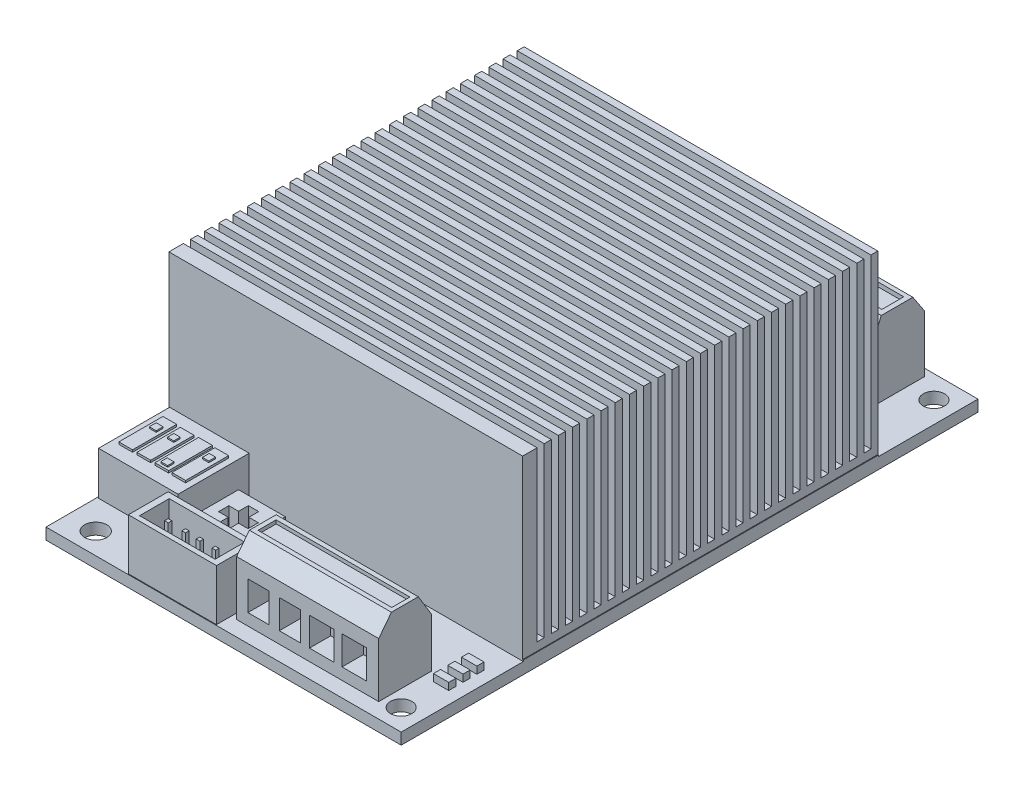
SolidWorks part; units mm, degrees
ref_plane "Front Plane" through (0, 0, 0) normal (0, 0, 1) x (1, 0, 0)
ref_plane "Top Plane" through (0, 0, 0) normal (0, 1, 0) x (1, 0, 0)
ref_plane "Right Plane" through (0, 0, 0) normal (1, 0, 0) x (0, 0, -1)
ref_plane "Plane1" through (0, 0, 0) normal (0, -1, 0) x (1, 0, 0)
sketch "Sketch1" plane through (0, 0, 0) normal (0, -1, 0) x (1, 0, 0)
  line L0 (50, -7.2) -> (0, -7.2)
  line L1 (0, -7.2) -> (0, -81.2)
  line L2 (0, -81.2) -> (50, -81.2)
  line L3 (50, -81.2) -> (50, -7.2)
extrude "Boss-Extrude1" add sketch "Sketch1" against normal blind 26.6
sketch "Sketch2" plane through (50, 0, 0) normal (1, 0, 0) x (0, 0, -1)
  line L0 (67.2, 26.6) -> (67.2, 1.6)
  line L1 (81.2, 1.6) -> (81.2, 26.6)
  line L2 (81.2, 26.6) -> (67.2, 26.6)
  spline S0 degree 1 poles (67.2, 1.6) (80, 1.6) (81.2, 1.6) knots 0 0 1 1.09375 1.09375
extrude "Cut-Extrude1" cut sketch "Sketch2" against normal through all
sketch "Sketch3" plane through (0, 0, -67.2) normal (0, 0, -1) x (-1, 0, 0)
  line L0 (-0.1, 26.6) -> (-0.1, 1.9034)
  line L1 (-0.1, 1.9034) -> (0, 1.9034)
  line L2 (0, 1.9034) -> (0, 26.6)
  line L3 (0, 26.6) -> (-0.1, 26.6)
extrude "Cut-Extrude2" cut sketch "Sketch3" against normal blind 60
sketch "Sketch4" plane through (0.1, 0, 0) normal (-1, 0, 0) x (0, 0, 1)
  line L0 (-17.2, 26.6) -> (-17.2, 7.7)
  line L1 (-17.2, 7.7) -> (-7.2, 7.7)
  line L2 (-7.2, 7.7) -> (-7.2, 26.6)
  line L3 (-7.2, 26.6) -> (-17.2, 26.6)
extrude "Cut-Extrude3" cut sketch "Sketch4" against normal through all
sketch "Sketch5" plane through (0.1, 0, 0) normal (-1, 0, 0) x (0, 0, 1)
  line L0 (-7.2, 7.7) -> (-17.2, 7.7)
  line L1 (-17.2, 7.7) -> (-17.2, 1.9034)
  line L2 (-17.2, 1.9034) -> (-7.2, 1.9034)
  line L3 (-7.2, 1.9034) -> (-7.2, 7.7)
extrude "Cut-Extrude4" cut sketch "Sketch5" against normal blind 0.1
ref_plane "Plane2" [suppressed] through (0, 0, -17.2) normal (0, 0, 1) x (1, 0, 0)
ref_plane "Plane3" through (0, 0, -17.4899) normal (0, 0, -1) x (-1, 0, 0)
sketch "Sketch7" plane through (0, 0, -17.4899) normal (0, 0, -1) x (-1, 0, 0)
  line L0 (-0.1, 1.9034) -> (-0.1, 8.072)
  line L1 (-0.1, 8.072) -> (-0.2, 8.072)
  line L2 (-0.2, 8.072) -> (-0.2, 1.9034)
  line L3 (-0.2, 1.9034) -> (-0.1, 1.9034)
extrude "Cut-Extrude5" [suppressed] cut sketch "Sketch7" against normal up to surface
sketch "Sketch8" plane through (0, 1.9034, 0) normal (0, 1, 0) x (-1, 0, 0)
  line L0 (0, -17.4899) -> (0, -7.2)
  line L1 (0, -7.2) -> (-0.2, -7.2)
  line L2 (-0.2, -7.2) -> (-0.2, -17.4899)
  line L3 (-0.2, -17.4899) -> (0, -17.4899)
extrude "Cut-Extrude6" cut sketch "Sketch8" against normal blind 0.3034
sketch "Sketch9" plane through (0, 0, -7.2) normal (0, 0, 1) x (1, 0, 0)
  line L0 (50, 0) -> (0, 0)
  line L1 (0, 0) -> (0, 1.6)
  line L2 (0, 1.6) -> (50, 1.6)
  line L3 (50, 1.6) -> (50, 0)
extrude "Boss-Extrude2" add sketch "Sketch9" along normal blind 7.2
ref_plane "Plane4" [suppressed] through (0, 1.6, 0) normal (0, 1, 0) x (1, 0, 0)
ref_plane "Plane5" [suppressed] through (0, 1.1135, 0) normal (0, -1, 0) x (1, 0, 0)
sketch "Sketch11" [suppressed] plane through (0, 1.1135, 0) normal (0, -1, 0) x (1, 0, 0)
  line L0 (0, -17.4899) -> (0.2, -17.4899)
  line L1 (0.2, -17.4899) -> (0.2, -6.7544)
  line L2 (0.2, -6.7544) -> (0, -6.7544)
  line L3 (0, -6.7544) -> (0, -17.4899)
extrude "Cut-Extrude7" [suppressed] cut sketch "Sketch11" against normal up to surface
ref_plane "Plane6" [suppressed] through (0, 1.1135, 0) normal (0, 1, 0) x (1, 0, 0)
ref_plane "Plane7" [suppressed] through (0, 1.0032, 0) normal (0, -1, 0) x (1, 0, 0)
sketch "Sketch13" [suppressed] plane through (0, 1.0032, 0) normal (0, -1, 0) x (1, 0, 0)
  line L0 (0.2, -17.4147) -> (0.2, -6.7544)
  line L1 (0.2, -6.7544) -> (0, -6.7544)
  line L2 (0, -6.7544) -> (0, -17.4147)
  line L3 (0, -17.4147) -> (0.2, -17.4147)
extrude "Cut-Extrude8" [suppressed] cut sketch "Sketch13" against normal up to surface
sketch "Sketch14" plane through (50, 0, 0) normal (1, 0, 0) x (0, 0, -1)
  line L0 (7.2, 7.7) -> (7.2, 1.6)
  line L1 (7.2, 1.6) -> (17.2, 1.6)
  line L2 (17.2, 1.6) -> (17.2, 7.7)
  line L3 (17.2, 7.7) -> (7.2, 7.7)
extrude "Cut-Extrude9" cut sketch "Sketch14" against normal blind 38.6
sketch "Sketch15" plane through (0, 0, -67.2) normal (0, 0, -1) x (-1, 0, 0)
  line L0 (-49.9, 1.7904) -> (-49.9, 26.6)
  line L1 (-49.9, 26.6) -> (-50, 26.6)
  line L2 (-50, 26.6) -> (-50, 1.7904)
  line L3 (-50, 1.7904) -> (-49.9, 1.7904)
extrude "Cut-Extrude10" cut sketch "Sketch15" against normal blind 50
sketch "Sketch16" plane through (0.1, 0, 0) normal (-1, 0, 0) x (0, 0, 1)
  line L0 (-65.2338, 26.6) -> (-66.2338, 26.6)
  line L1 (-66.2338, 26.6) -> (-66.2338, 2.9373)
  line L2 (-66.2338, 2.9373) -> (-65.2338, 2.9373)
  line L3 (-65.2338, 2.9373) -> (-65.2338, 26.6)
extrude "Cut-Extrude11" cut sketch "Sketch16" against normal through all
sketch "Sketch17" plane through (0.1, 0, 0) normal (-1, 0, 0) x (0, 0, 1)
  line L0 (-63.2338, 26.6) -> (-64.2338, 26.6)
  line L1 (-64.2338, 26.6) -> (-64.2338, 2.9373)
  line L2 (-64.2338, 2.9373) -> (-63.2338, 2.9373)
  line L3 (-63.2338, 2.9373) -> (-63.2338, 26.6)
extrude "Cut-Extrude12" cut sketch "Sketch17" against normal through all
sketch "Sketch18" plane through (0.1, 0, 0) normal (-1, 0, 0) x (0, 0, 1)
  line L0 (-61.2338, 26.6) -> (-62.2338, 26.6)
  line L1 (-62.2338, 26.6) -> (-62.2338, 2.9373)
  line L2 (-62.2338, 2.9373) -> (-61.2338, 2.9373)
  line L3 (-61.2338, 2.9373) -> (-61.2338, 26.6)
extrude "Cut-Extrude13" cut sketch "Sketch18" against normal through all
sketch "Sketch19" plane through (0.1, 0, 0) normal (-1, 0, 0) x (0, 0, 1)
  line L0 (-59.2338, 26.6) -> (-60.2338, 26.6)
  line L1 (-60.2338, 26.6) -> (-60.2338, 2.9373)
  line L2 (-60.2338, 2.9373) -> (-59.2338, 2.9373)
  line L3 (-59.2338, 2.9373) -> (-59.2338, 26.6)
extrude "Cut-Extrude14" cut sketch "Sketch19" against normal through all
sketch "Sketch20" plane through (0.1, 0, 0) normal (-1, 0, 0) x (0, 0, 1)
  line L0 (-57.2338, 26.6) -> (-58.2338, 26.6)
  line L1 (-58.2338, 26.6) -> (-58.2338, 2.9373)
  line L2 (-58.2338, 2.9373) -> (-57.2338, 2.9373)
  line L3 (-57.2338, 2.9373) -> (-57.2338, 26.6)
extrude "Cut-Extrude15" cut sketch "Sketch20" against normal through all
sketch "Sketch21" plane through (0.1, 0, 0) normal (-1, 0, 0) x (0, 0, 1)
  line L0 (-55.2338, 26.6) -> (-56.2338, 26.6)
  line L1 (-56.2338, 26.6) -> (-56.2338, 2.9373)
  line L2 (-56.2338, 2.9373) -> (-55.2338, 2.9373)
  line L3 (-55.2338, 2.9373) -> (-55.2338, 26.6)
extrude "Cut-Extrude16" cut sketch "Sketch21" against normal through all
sketch "Sketch22" plane through (0.1, 0, 0) normal (-1, 0, 0) x (0, 0, 1)
  line L0 (-53.2338, 26.6) -> (-54.2338, 26.6)
  line L1 (-54.2338, 26.6) -> (-54.2338, 2.9373)
  line L2 (-54.2338, 2.9373) -> (-53.2338, 2.9373)
  line L3 (-53.2338, 2.9373) -> (-53.2338, 26.6)
extrude "Cut-Extrude17" cut sketch "Sketch22" against normal through all
sketch "Sketch23" plane through (0.1, 0, 0) normal (-1, 0, 0) x (0, 0, 1)
  line L0 (-51.2338, 26.6) -> (-52.2338, 26.6)
  line L1 (-52.2338, 26.6) -> (-52.2338, 2.9373)
  line L2 (-52.2338, 2.9373) -> (-51.2338, 2.9373)
  line L3 (-51.2338, 2.9373) -> (-51.2338, 26.6)
extrude "Cut-Extrude18" cut sketch "Sketch23" against normal through all
sketch "Sketch24" plane through (0.1, 0, 0) normal (-1, 0, 0) x (0, 0, 1)
  line L0 (-49.2338, 26.6) -> (-50.2338, 26.6)
  line L1 (-50.2338, 26.6) -> (-50.2338, 2.9373)
  line L2 (-50.2338, 2.9373) -> (-49.2338, 2.9373)
  line L3 (-49.2338, 2.9373) -> (-49.2338, 26.6)
extrude "Cut-Extrude19" cut sketch "Sketch24" against normal through all
sketch "Sketch25" plane through (0.1, 0, 0) normal (-1, 0, 0) x (0, 0, 1)
  line L0 (-47.2338, 26.6) -> (-48.2338, 26.6)
  line L1 (-48.2338, 26.6) -> (-48.2338, 2.9373)
  line L2 (-48.2338, 2.9373) -> (-47.2338, 2.9373)
  line L3 (-47.2338, 2.9373) -> (-47.2338, 26.6)
extrude "Cut-Extrude20" cut sketch "Sketch25" against normal through all
sketch "Sketch26" plane through (0.1, 0, 0) normal (-1, 0, 0) x (0, 0, 1)
  line L0 (-45.2338, 26.6) -> (-46.2338, 26.6)
  line L1 (-46.2338, 26.6) -> (-46.2338, 2.9373)
  line L2 (-46.2338, 2.9373) -> (-45.2338, 2.9373)
  line L3 (-45.2338, 2.9373) -> (-45.2338, 26.6)
extrude "Cut-Extrude21" cut sketch "Sketch26" against normal through all
sketch "Sketch27" plane through (0.1, 0, 0) normal (-1, 0, 0) x (0, 0, 1)
  line L0 (-43.2338, 26.6) -> (-44.2338, 26.6)
  line L1 (-44.2338, 26.6) -> (-44.2338, 2.9373)
  line L2 (-44.2338, 2.9373) -> (-43.2338, 2.9373)
  line L3 (-43.2338, 2.9373) -> (-43.2338, 26.6)
extrude "Cut-Extrude22" cut sketch "Sketch27" against normal through all
sketch "Sketch28" plane through (0.1, 0, 0) normal (-1, 0, 0) x (0, 0, 1)
  line L0 (-41.2338, 26.6) -> (-42.2338, 26.6)
  line L1 (-42.2338, 26.6) -> (-42.2338, 2.9373)
  line L2 (-42.2338, 2.9373) -> (-41.2338, 2.9373)
  line L3 (-41.2338, 2.9373) -> (-41.2338, 26.6)
extrude "Cut-Extrude23" cut sketch "Sketch28" against normal through all
sketch "Sketch29" plane through (0.1, 0, 0) normal (-1, 0, 0) x (0, 0, 1)
  line L0 (-39.2338, 26.6) -> (-40.2338, 26.6)
  line L1 (-40.2338, 26.6) -> (-40.2338, 2.9373)
  line L2 (-40.2338, 2.9373) -> (-39.2338, 2.9373)
  line L3 (-39.2338, 2.9373) -> (-39.2338, 26.6)
extrude "Cut-Extrude24" cut sketch "Sketch29" against normal through all
sketch "Sketch30" plane through (0.1, 0, 0) normal (-1, 0, 0) x (0, 0, 1)
  line L0 (-37.2338, 26.6) -> (-38.2338, 26.6)
  line L1 (-38.2338, 26.6) -> (-38.2338, 2.9373)
  line L2 (-38.2338, 2.9373) -> (-37.2338, 2.9373)
  line L3 (-37.2338, 2.9373) -> (-37.2338, 26.6)
extrude "Cut-Extrude25" cut sketch "Sketch30" against normal through all
sketch "Sketch31" plane through (0.1, 0, 0) normal (-1, 0, 0) x (0, 0, 1)
  line L0 (-35.2338, 26.6) -> (-36.2338, 26.6)
  line L1 (-36.2338, 26.6) -> (-36.2338, 2.9373)
  line L2 (-36.2338, 2.9373) -> (-35.2338, 2.9373)
  line L3 (-35.2338, 2.9373) -> (-35.2338, 26.6)
extrude "Cut-Extrude26" cut sketch "Sketch31" against normal through all
sketch "Sketch32" plane through (0.1, 0, 0) normal (-1, 0, 0) x (0, 0, 1)
  line L0 (-33.2338, 26.6) -> (-34.2338, 26.6)
  line L1 (-34.2338, 26.6) -> (-34.2338, 2.9373)
  line L2 (-34.2338, 2.9373) -> (-33.2338, 2.9373)
  line L3 (-33.2338, 2.9373) -> (-33.2338, 26.6)
extrude "Cut-Extrude27" cut sketch "Sketch32" against normal through all
sketch "Sketch33" plane through (0.1, 0, 0) normal (-1, 0, 0) x (0, 0, 1)
  line L0 (-31.2338, 26.6) -> (-32.2338, 26.6)
  line L1 (-32.2338, 26.6) -> (-32.2338, 2.9373)
  line L2 (-32.2338, 2.9373) -> (-31.2338, 2.9373)
  line L3 (-31.2338, 2.9373) -> (-31.2338, 26.6)
extrude "Cut-Extrude28" cut sketch "Sketch33" against normal through all
sketch "Sketch34" plane through (0.1, 0, 0) normal (-1, 0, 0) x (0, 0, 1)
  line L0 (-29.2338, 26.6) -> (-30.2338, 26.6)
  line L1 (-30.2338, 26.6) -> (-30.2338, 2.9373)
  line L2 (-30.2338, 2.9373) -> (-29.2338, 2.9373)
  line L3 (-29.2338, 2.9373) -> (-29.2338, 26.6)
extrude "Cut-Extrude29" cut sketch "Sketch34" against normal through all
sketch "Sketch35" plane through (0.1, 0, 0) normal (-1, 0, 0) x (0, 0, 1)
  line L0 (-27.2338, 26.6) -> (-28.2338, 26.6)
  line L1 (-28.2338, 26.6) -> (-28.2338, 2.9373)
  line L2 (-28.2338, 2.9373) -> (-27.2338, 2.9373)
  line L3 (-27.2338, 2.9373) -> (-27.2338, 26.6)
extrude "Cut-Extrude30" cut sketch "Sketch35" against normal through all
sketch "Sketch36" plane through (0.1, 0, 0) normal (-1, 0, 0) x (0, 0, 1)
  line L0 (-25.2338, 26.6) -> (-26.2338, 26.6)
  line L1 (-26.2338, 26.6) -> (-26.2338, 2.9373)
  line L2 (-26.2338, 2.9373) -> (-25.2338, 2.9373)
  line L3 (-25.2338, 2.9373) -> (-25.2338, 26.6)
extrude "Cut-Extrude31" cut sketch "Sketch36" against normal through all
sketch "Sketch37" plane through (0.1, 0, 0) normal (-1, 0, 0) x (0, 0, 1)
  line L0 (-23.2338, 26.6) -> (-24.2338, 26.6)
  line L1 (-24.2338, 26.6) -> (-24.2338, 2.9373)
  line L2 (-24.2338, 2.9373) -> (-23.2338, 2.9373)
  line L3 (-23.2338, 2.9373) -> (-23.2338, 26.6)
extrude "Cut-Extrude32" cut sketch "Sketch37" against normal through all
sketch "Sketch38" plane through (0.1, 0, 0) normal (-1, 0, 0) x (0, 0, 1)
  line L0 (-21.2338, 26.6) -> (-22.2338, 26.6)
  line L1 (-22.2338, 26.6) -> (-22.2338, 2.9373)
  line L2 (-22.2338, 2.9373) -> (-21.2338, 2.9373)
  line L3 (-21.2338, 2.9373) -> (-21.2338, 26.6)
extrude "Cut-Extrude33" cut sketch "Sketch38" against normal through all
sketch "Sketch39" plane through (0.1, 0, 0) normal (-1, 0, 0) x (0, 0, 1)
  line L0 (-19.2338, 26.6) -> (-20.2338, 26.6)
  line L1 (-20.2338, 26.6) -> (-20.2338, 2.9373)
  line L2 (-20.2338, 2.9373) -> (-19.2338, 2.9373)
  line L3 (-19.2338, 2.9373) -> (-19.2338, 26.6)
extrude "Cut-Extrude34" cut sketch "Sketch39" against normal through all
sketch "Sketch40" plane through (0, 1.6, 0) normal (0, 1, 0) x (-1, 0, 0)
  line L0 (-46.1084, -13.3828) -> (-48.2829, -13.3828)
  line L1 (-48.2829, -13.3828) -> (-48.2829, -12.377)
  line L2 (-48.2829, -12.377) -> (-46.1084, -12.377)
  line L3 (-46.1084, -12.377) -> (-46.1084, -13.3828)
extrude "Boss-Extrude3" add sketch "Sketch40" along normal blind 1
sketch "Sketch41" plane through (0, 1.6, 0) normal (0, 1, 0) x (-1, 0, 0)
  line L0 (-46.1356, -11.4257) -> (-48.2829, -11.4257)
  line L1 (-48.2829, -11.4257) -> (-48.2829, -10.42)
  line L2 (-48.2829, -10.42) -> (-46.1356, -10.42)
  line L3 (-46.1356, -10.42) -> (-46.1356, -11.4257)
extrude "Boss-Extrude4" add sketch "Sketch41" along normal blind 1
sketch "Sketch42" plane through (0, 1.6, 0) normal (0, 1, 0) x (-1, 0, 0)
  line L0 (-46.1356, -9.4142) -> (-48.2829, -9.4142)
  line L1 (-48.2829, -9.4142) -> (-48.2829, -8.4085)
  line L2 (-48.2829, -8.4085) -> (-46.1356, -8.4085)
  line L3 (-46.1356, -8.4085) -> (-46.1356, -9.4142)
extrude "Boss-Extrude5" add sketch "Sketch42" along normal blind 1
sketch "Sketch43" plane through (0, 7.7, 0) normal (0, 1, 0) x (-1, 0, 0)
  line L0 (-5.6278, -15.2126) -> (-5.6278, -9.1046)
  line L1 (-5.6278, -9.1046) -> (-3.6949, -9.1046)
  line L2 (-3.6949, -9.1046) -> (-3.6949, -15.2126)
  line L3 (-3.6949, -15.2126) -> (-5.6278, -15.2126)
extrude "Boss-Extrude6" add sketch "Sketch43" along normal blind 0.3
sketch "Sketch44" plane through (0, 8, 0) normal (0, 1, 0) x (-1, 0, 0)
  line L0 (-5.0896, -13.8034) -> (-5.0896, -12.9014)
  line L1 (-5.0896, -12.9014) -> (-4.1876, -12.9014)
  line L2 (-4.1876, -12.9014) -> (-4.1876, -13.8034)
  line L3 (-4.1876, -13.8034) -> (-5.0896, -13.8034)
extrude "Boss-Extrude7" add sketch "Sketch44" along normal blind 0.2
sketch "Sketch45" plane through (0, 7.7, 0) normal (0, 1, 0) x (-1, 0, 0)
  line L0 (-8.1535, -15.2642) -> (-8.1535, -9.1046)
  line L1 (-8.1535, -9.1046) -> (-6.2206, -9.1046)
  line L2 (-6.2206, -9.1046) -> (-6.2206, -15.2642)
  line L3 (-6.2206, -15.2642) -> (-8.1535, -15.2642)
extrude "Boss-Extrude8" add sketch "Sketch45" along normal blind 0.3
sketch "Sketch46" plane through (0, 8, 0) normal (0, 1, 0) x (-1, 0, 0)
  line L0 (-7.6668, -10.3564) -> (-7.6668, -9.4544)
  line L1 (-7.6668, -9.4544) -> (-6.7004, -9.4544)
  line L2 (-6.7004, -9.4544) -> (-6.7004, -10.3564)
  line L3 (-6.7004, -10.3564) -> (-7.6668, -10.3564)
extrude "Boss-Extrude9" add sketch "Sketch46" along normal blind 0.2
sketch "Sketch47" plane through (0, 7.7, 0) normal (0, 1, 0) x (-1, 0, 0)
  line L0 (-10.5503, -15.1611) -> (-10.5503, -9.1046)
  line L1 (-10.5503, -9.1046) -> (-8.6174, -9.1046)
  line L2 (-8.6174, -9.1046) -> (-8.6174, -15.1611)
  line L3 (-8.6174, -15.1611) -> (-10.5503, -15.1611)
extrude "Boss-Extrude10" add sketch "Sketch47" along normal blind 0.3
sketch "Sketch48" plane through (0, 8, 0) normal (0, 1, 0) x (-1, 0, 0)
  line L0 (-10.0186, -13.8679) -> (-10.0186, -12.9014)
  line L1 (-10.0186, -12.9014) -> (-9.1165, -12.9014)
  line L2 (-9.1165, -12.9014) -> (-9.1165, -13.8679)
  line L3 (-9.1165, -13.8679) -> (-10.0186, -13.8679)
extrude "Boss-Extrude11" add sketch "Sketch48" along normal blind 0.2
sketch "Sketch49" plane through (0, 7.7, 0) normal (0, 1, 0) x (-1, 0, 0)
  line L0 (-3.0763, -15.3157) -> (-3.0763, -9.1046)
  line L1 (-3.0763, -9.1046) -> (-1.1434, -9.1046)
  line L2 (-1.1434, -9.1046) -> (-1.1434, -15.3157)
  line L3 (-1.1434, -15.3157) -> (-3.0763, -15.3157)
extrude "Boss-Extrude12" add sketch "Sketch49" along normal blind 0.3
sketch "Sketch50" plane through (0, 8, 0) normal (0, 1, 0) x (-1, 0, 0)
  line L0 (-2.609, -13.8679) -> (-2.609, -12.9014)
  line L1 (-2.609, -12.9014) -> (-1.6426, -12.9014)
  line L2 (-1.6426, -12.9014) -> (-1.6426, -13.8679)
  line L3 (-1.6426, -13.8679) -> (-2.609, -13.8679)
extrude "Boss-Extrude13" add sketch "Sketch50" along normal blind 0.2
sketch "Sketch51" plane through (0, 1.6, 0) normal (0, 1, 0) x (-1, 0, 0)
  line L0 (-11.5, -5.7) -> (-23.9, -5.7)
  line L1 (-23.9, -5.7) -> (-23.9, -0.1)
  line L2 (-23.9, -0.1) -> (-11.5, -0.1)
  line L3 (-11.5, -0.1) -> (-11.5, -5.7)
extrude "Boss-Extrude14" add sketch "Sketch51" along normal blind 7.2
sketch "Sketch52" plane through (0, 8.8, 0) normal (0, 1, 0) x (-1, 0, 0)
  line L0 (-23.024, -0.772) -> (-23.024, -4.9368)
  line L1 (-23.024, -4.9368) -> (-12.4058, -4.9368)
  line L2 (-12.4058, -4.9368) -> (-12.4058, -0.772)
  line L3 (-12.4058, -0.772) -> (-23.024, -0.772)
extrude "Cut-Extrude35" cut sketch "Sketch52" against normal blind 5
sketch "Sketch53" plane through (0, 3.8, 0) normal (0, 1, 0) x (-1, 0, 0)
  line L0 (-14.6948, -3.0202) -> (-14.6948, -2.5089)
  line L1 (-14.6948, -2.5089) -> (-14.1835, -2.5089)
  line L2 (-14.1835, -2.5089) -> (-14.1835, -3.0202)
  line L3 (-14.1835, -3.0202) -> (-14.6948, -3.0202)
extrude "Boss-Extrude15" add sketch "Sketch53" along normal blind 4.4
sketch "Sketch54" plane through (0, 3.8, 0) normal (0, 1, 0) x (-1, 0, 0)
  line L0 (-17.136, -3.0202) -> (-17.136, -2.5089)
  line L1 (-17.136, -2.5089) -> (-16.6246, -2.5089)
  line L2 (-16.6246, -2.5089) -> (-16.6246, -3.0202)
  line L3 (-16.6246, -3.0202) -> (-17.136, -3.0202)
extrude "Boss-Extrude16" add sketch "Sketch54" along normal blind 4.4
sketch "Sketch55" plane through (0, 3.8, 0) normal (0, 1, 0) x (-1, 0, 0)
  line L0 (-19.1482, -3.0037) -> (-19.1482, -2.5089)
  line L1 (-19.1482, -2.5089) -> (-18.6369, -2.5089)
  line L2 (-18.6369, -2.5089) -> (-18.6369, -3.0037)
  line L3 (-18.6369, -3.0037) -> (-19.1482, -3.0037)
extrude "Boss-Extrude17" add sketch "Sketch55" along normal blind 4.4
sketch "Sketch56" plane through (0, 3.8, 0) normal (0, 1, 0) x (-1, 0, 0)
  line L0 (-21.3585, -2.9872) -> (-21.3585, -2.5089)
  line L1 (-21.3585, -2.5089) -> (-20.8472, -2.5089)
  line L2 (-20.8472, -2.5089) -> (-20.8472, -2.9872)
  line L3 (-20.8472, -2.9872) -> (-21.3585, -2.9872)
extrude "Boss-Extrude18" add sketch "Sketch56" along normal blind 4.4
sketch "Sketch57" plane through (0, 1.6, 0) normal (0, 1, 0) x (-1, 0, 0)
  line L0 (-14, -13.1) -> (-20.6, -13.1)
  line L1 (-20.6, -13.1) -> (-20.6, -6.5)
  line L2 (-20.6, -6.5) -> (-14, -6.5)
  line L3 (-14, -6.5) -> (-14, -13.1)
extrude "Boss-Extrude19" add sketch "Sketch57" along normal blind 5
sketch "Sketch58" plane through (0, 6.6, 0) normal (0, 1, 0) x (-1, 0, 0)
  line L0 (-18.0861, -10.471) -> (-18.0861, -11.8565)
  line L1 (-18.0861, -11.8565) -> (-16.6346, -11.8565)
  line L2 (-16.6346, -11.8565) -> (-16.6346, -10.471)
  line L3 (-16.6346, -10.471) -> (-15.2656, -10.471)
  line L4 (-15.2656, -10.471) -> (-15.2656, -9.0195)
  line L5 (-15.2656, -9.0195) -> (-16.6346, -9.0195)
  line L6 (-16.6346, -9.0195) -> (-16.6346, -7.5185)
  line L7 (-16.6346, -7.5185) -> (-18.0861, -7.5185)
  line L8 (-18.0861, -7.5185) -> (-18.0861, -9.0195)
  line L9 (-18.0861, -9.0195) -> (-19.4222, -9.0195)
  line L10 (-19.4222, -9.0195) -> (-19.4222, -10.471)
  line L11 (-19.4222, -10.471) -> (-18.0861, -10.471)
extrude "Cut-Extrude36" cut sketch "Sketch58" against normal blind 4.3
sketch "Sketch59" plane through (0, 1.6, 0) normal (0, 1, 0) x (-1, 0, 0)
  line L0 (-24.7, -9.5359) -> (-44.7, -9.5359)
  line L1 (-44.7, -9.5359) -> (-44.7, -2.1359)
  line L2 (-44.7, -2.1359) -> (-24.7, -2.1359)
  line L3 (-24.7, -2.1359) -> (-24.7, -9.5359)
extrude "Boss-Extrude20" add sketch "Sketch59" along normal blind 10
sketch "Sketch60" plane through (0, 11.6, 0) normal (0, 1, 0) x (-1, 0, 0)
  line L0 (-44.1451, -7.0768) -> (-25.3218, -7.0768)
  line L1 (-25.3218, -7.0768) -> (-25.3218, -4.5285)
  line L2 (-25.3218, -4.5285) -> (-44.1451, -4.5285)
  line L3 (-44.1451, -4.5285) -> (-44.1451, -7.0768)
extrude "Cut-Extrude37" cut sketch "Sketch60" against normal blind 0.5
sketch "Sketch61" plane through (0, 0, -2.1359) normal (0, 0, 1) x (1, 0, 0)
  line L0 (29.2826, 3.2447) -> (29.2826, 7.3617)
  line L1 (29.2826, 7.3617) -> (26.287, 7.3617)
  line L2 (26.287, 7.3617) -> (26.287, 3.2447)
  line L3 (26.287, 3.2447) -> (29.2826, 3.2447)
extrude "Cut-Extrude38" cut sketch "Sketch61" against normal blind 3
sketch "Sketch62" plane through (0, 0, -2.1359) normal (0, 0, 1) x (1, 0, 0)
  line L0 (33.7066, 3.2447) -> (33.7066, 7.2958)
  line L1 (33.7066, 7.2958) -> (30.711, 7.2958)
  line L2 (30.711, 7.2958) -> (30.711, 3.2447)
  line L3 (30.711, 3.2447) -> (33.7066, 3.2447)
extrude "Cut-Extrude39" cut sketch "Sketch62" against normal blind 3
sketch "Sketch63" plane through (0, 0, -2.1359) normal (0, 0, 1) x (1, 0, 0)
  line L0 (38.3835, 3.2447) -> (38.3835, 7.2629)
  line L1 (38.3835, 7.2629) -> (34.9484, 7.2629)
  line L2 (34.9484, 7.2629) -> (34.9484, 3.2447)
  line L3 (34.9484, 3.2447) -> (38.3835, 3.2447)
extrude "Cut-Extrude40" cut sketch "Sketch63" against normal blind 3
sketch "Sketch64" plane through (0, 0, -2.1359) normal (0, 0, 1) x (1, 0, 0)
  line L0 (42.9715, 3.2447) -> (42.9715, 7.2958)
  line L1 (42.9715, 7.2958) -> (39.5363, 7.2958)
  line L2 (39.5363, 7.2958) -> (39.5363, 3.2447)
  line L3 (39.5363, 3.2447) -> (42.9715, 3.2447)
extrude "Cut-Extrude41" cut sketch "Sketch64" against normal blind 3
sketch "Sketch65" plane through (0, 1.6, 0) normal (0, 1, 0) x (-1, 0, 0)
  spline S0 degree 1 poles (-13.5, -80.2) (-43.5, -80.2) knots 0 0 1 1
  spline S1 degree 1 poles (-43.5, -80.2) (-43.5, -72.7) knots 0 0 1 1
  spline S2 degree 1 poles (-13.5, -72.7) (-43.5, -72.7) knots 0 0 1 1
  spline S3 degree 1 poles (-13.5, -80.2) (-13.5, -72.7) knots 0 0 1 1
extrude "Boss-Extrude21" add sketch "Sketch65" along normal blind 10.5
sketch "Sketch66" plane through (0, 0, -80.2) normal (0, 0, -1) x (-1, 0, 0)
  line L0 (-39.9219, 3.3672) -> (-39.9219, 6.3644)
  line L1 (-39.9219, 6.3644) -> (-42.1286, 6.3644)
  line L2 (-42.1286, 6.3644) -> (-42.1286, 3.3672)
  line L3 (-42.1286, 3.3672) -> (-39.9219, 3.3672)
extrude "Cut-Extrude42" cut sketch "Sketch66" against normal blind 1.3
sketch "Sketch67" plane through (0, 0, -80.2) normal (0, 0, -1) x (-1, 0, 0)
  line L0 (-28.4601, 3.3672) -> (-26.2534, 3.3672)
  line L1 (-26.2534, 3.3672) -> (-26.2534, 6.6608)
  line L2 (-26.2534, 6.6608) -> (-28.4601, 6.6608)
  line L3 (-28.4601, 6.6608) -> (-28.4601, 3.3672)
extrude "Cut-Extrude43" cut sketch "Sketch67" against normal blind 1.3
sketch "Sketch68" plane through (0, 0, -80.2) normal (0, 0, -1) x (-1, 0, 0)
  line L0 (-24.8042, 3.3672) -> (-22.5975, 3.3672)
  line L1 (-22.5975, 3.3672) -> (-22.5975, 6.6279)
  line L2 (-22.5975, 6.6279) -> (-24.8042, 6.6279)
  line L3 (-24.8042, 6.6279) -> (-24.8042, 3.3672)
extrude "Cut-Extrude44" cut sketch "Sketch68" against normal blind 1.3
sketch "Sketch69" plane through (0, 0, -80.2) normal (0, 0, -1) x (-1, 0, 0)
  line L0 (-21.0824, 3.3672) -> (-18.8757, 3.3672)
  line L1 (-18.8757, 3.3672) -> (-18.8757, 6.5949)
  line L2 (-18.8757, 6.5949) -> (-21.0824, 6.5949)
  line L3 (-21.0824, 6.5949) -> (-21.0824, 3.3672)
extrude "Cut-Extrude45" cut sketch "Sketch69" against normal blind 1.3
sketch "Sketch70" plane through (0, 0, -80.2) normal (0, 0, -1) x (-1, 0, 0)
  line L0 (-17.2618, 3.3672) -> (-15.0551, 3.3672)
  line L1 (-15.0551, 3.3672) -> (-15.0551, 6.5949)
  line L2 (-15.0551, 6.5949) -> (-17.2618, 6.5949)
  line L3 (-17.2618, 6.5949) -> (-17.2618, 3.3672)
extrude "Cut-Extrude46" cut sketch "Sketch70" against normal blind 1.3
sketch "Sketch71" plane through (0, 0, -80.2) normal (0, 0, -1) x (-1, 0, 0)
  line L0 (-32.5112, 3.3672) -> (-32.5112, 6.2985)
  line L1 (-32.5112, 6.2985) -> (-34.718, 6.2985)
  line L2 (-34.718, 6.2985) -> (-34.718, 3.3672)
  line L3 (-34.718, 3.3672) -> (-32.5112, 3.3672)
extrude "Cut-Extrude47" cut sketch "Sketch71" against normal blind 1.3
sketch "Sketch72" plane through (0, 0, -80.2) normal (0, 0, -1) x (-1, 0, 0)
  line L0 (-36.0354, 3.3672) -> (-36.0354, 6.2985)
  line L1 (-36.0354, 6.2985) -> (-38.2421, 6.2985)
  line L2 (-38.2421, 6.2985) -> (-38.2421, 3.3672)
  line L3 (-38.2421, 3.3672) -> (-36.0354, 3.3672)
extrude "Cut-Extrude48" cut sketch "Sketch72" against normal blind 1.3
sketch "Sketch73" plane through (0, 12.1, 0) normal (0, 1, 0) x (-1, 0, 0)
  line L0 (-42.8056, -77.9454) -> (-14.4029, -77.9454)
  line L1 (-14.4029, -77.9454) -> (-14.4029, -74.8662)
  line L2 (-14.4029, -74.8662) -> (-42.8056, -74.8662)
  line L3 (-42.8056, -74.8662) -> (-42.8056, -77.9454)
extrude "Cut-Extrude49" cut sketch "Sketch73" against normal blind 0.6
ref_plane "Plane8" [suppressed] through (17.316, 0, 0) normal (1, 0, 0) x (0, 0, -1)
sketch "Sketch74" [suppressed] plane through (17.316, 0, 0) normal (1, 0, 0) x (0, 0, -1)
  line L0 (9.8291, 6.6) -> (7.1071, 6.6)
  line L1 (7.1071, 6.6) -> (7.1071, 5.2)
  line L2 (7.1071, 5.2) -> (9.8291, 5.2)
  line L3 (9.8291, 5.2) -> (9.8291, 6.6)
  line L4 (9.8291, 5.2) -> (9.8291, 6.6) construction
revolve "Cut-Revolve1" [suppressed] cut sketch "Sketch74" angle 360 about L4 reverse direction yes
ref_plane "Plane9" [suppressed] through (0, 0, -75.45) normal (0, 0, -1) x (-1, 0, 0)
sketch "Sketch75" [suppressed] plane through (0, 0, -75.45) normal (0, 0, -1) x (-1, 0, 0)
  line L0 (-10.1, 1.6) -> (-5.05, 1.6)
  line L1 (-5.05, 1.6) -> (-5.05, 22.3)
  line L2 (-5.05, 22.3) -> (-10.1, 22.3)
  line L3 (-10.1, 22.3) -> (-10.1, 1.6)
  line L4 (-5.05, 1.6) -> (-5.05, 22.3) construction
revolve "Revolve1" [suppressed] add sketch "Sketch75" angle 360 about L4 reverse direction yes
chamfer "Chamfer1" distance 2.5229 angle 33.509 1 edges first distance on face at (37.1388, 4.8328, -80.2)
chamfer "Chamfer2" distance 3.0052 angle 31.355 1 edges at (34.7, 11.6, -9.5359) first distance on face at (34.7, 6.6, -9.5359)
chamfer "Chamfer3" distance 3.1345 angle 23.741 1 edges first distance on face at (21, 6.85, -72.7)
chamfer "Chamfer4" distance 2.3147 angle 37.722 1 edges at (34.7, 11.6, -2.1359) first distance on face at (41.2539, 5.2703, -2.1359)
fillet "Fillet1" [suppressed] radius 1.2 tangent propagation no
sketch "Sketch76" plane through (0, 0, 0) normal (0, -1, 0) x (1, 0, 0)
  line L0 (0, 0) -> (4, 0) construction
  line L1 (0, 0) -> (50, 0) construction
  line L2 (4, 0) -> (4, -3) construction
  line L3 (4, -3) -> (47, -3) construction
  line L4 (47, -3) -> (47, -78) construction
  line L5 (0, -78) -> (11.5, -78) construction
  line L6 (0, 0) -> (0, -81.2) construction
  circle A0 centre (4, -3) radius 1.56
  circle A1 centre (47, -3) radius 1.5
  circle A2 centre (47, -78) radius 1.5
  circle A3 centre (11.5, -78) radius 1.5
extrude "Cut-Extrude50" cut sketch "Sketch76" against normal blind 10
